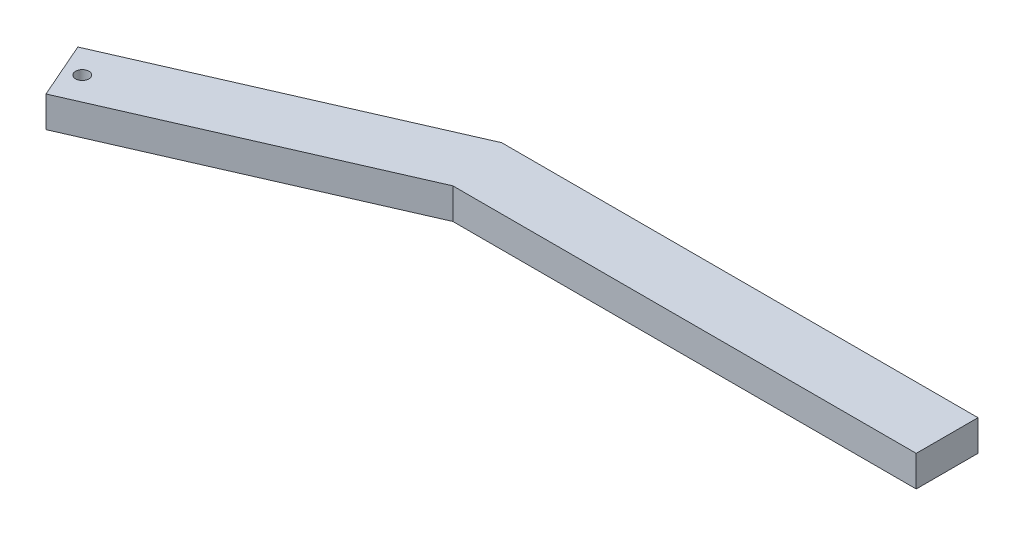
SolidWorks part; units mm, degrees
ref_plane "Front Plane" through (0, 0, 0) normal (0, 0, 1) x (1, 0, 0)
ref_plane "Top Plane" through (0, 0, 0) normal (0, 1, 0) x (1, 0, 0)
ref_plane "Right Plane" through (0, 0, 0) normal (1, 0, 0) x (0, 0, -1)
sketch "Sketch1" plane through (0, 0, 0) normal (0, 1, 0) x (1, 0, 0)
  line L0 (0, 0) -> (242.4215, 106.1223)
  line L1 (242.4215, 106.1223) -> (634.0535, 106.1223)
  line L2 (634.0535, 106.1223) -> (634.0535, 55.3223)
  line L3 (634.0535, 55.3223) -> (253.0535, 55.3223)
  line L4 (253.0535, 55.3223) -> (20.3717, -46.5364)
  line L5 (20.3717, -46.5364) -> (0, 0)
  dimension "D1" = 381
  dimension "D2" = 254
  dimension "D3" = 50.8
  dimension "D4" = 50.8
extrude "Boss-Extrude1" add sketch "Sketch1" along normal blind 25.4
hole_wizard "CSK for M10 Countersunk Flat Head Screw1" positions "Sketch4" profile "Sketch5" countersink size "M10" standard "DIN" end condition through all
sketch "Sketch4" plane through (0, 0, 0) normal (0, 1, 0) x (1, 0, 0)
  line L0 (10.1859, -23.2682) -> (56.9634, -2.7909) construction
  line L1 (0, 0) -> (20.3717, -46.5364) construction
  line L2 (0, 0) -> (20.3717, -46.5364) construction
  point P0 (21.82, -18.1752)
  dimension "D1" = 12.7
sketch "Sketch5" plane through (21.82, 0, 18.1752) normal (1, 0, 0) x (0, 0, -1)
  line L0 (0, 0) -> (0, 25.4)
  line L1 (0, 25.4) -> (5.5, 25.4)
  line L2 (5.5, 25.4) -> (5.5, 4.5)
  line L3 (5.5, 4.5) -> (10, 0)
  line L5 (10, 0) -> (0, 0)
  line L6 (-5.5, 4.5) -> (-10, 0) construction
  line L11 (0, -6.35) -> (0, 107.95) construction
  dimension "Thru Hole Dia." = 11
  dimension "Thru Hole Depth" = 25.4
  dimension "Near C'Sink Dia." = 20
  dimension "Near C'Sink Angle" = 90
